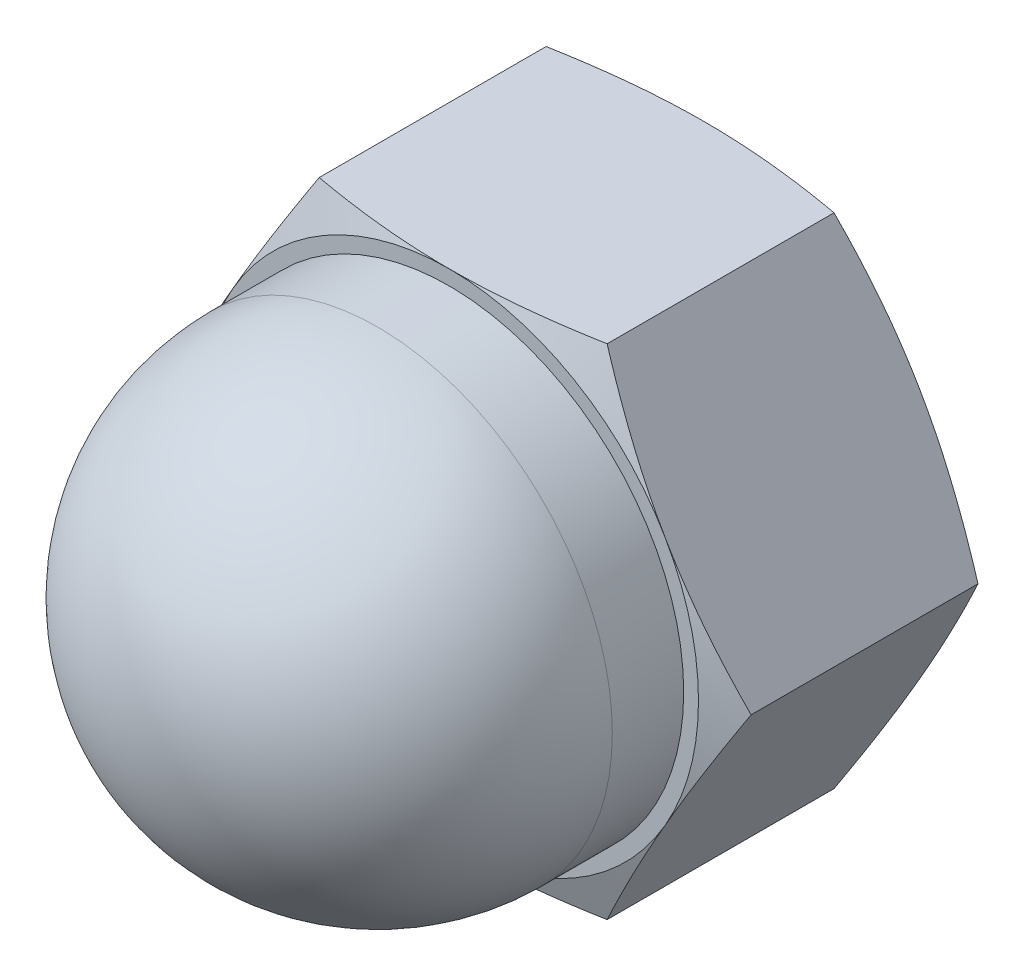
SolidWorks part; units mm, degrees
ref_plane "Front" through (0, 0, 0) normal (0, 0, 1) x (1, 0, 0)
ref_plane "Top" through (0, 0, 0) normal (0, 1, 0) x (1, 0, 0)
ref_plane "Right" through (0, 0, 0) normal (1, 0, 0) x (0, 0, -1)
sketch "Sketch1" plane through (0, 0, 0) normal (0, 0, 1) x (1, 0, 0)
  line L1 (5.6465, 0) -> (2.8232, 4.89)
  line L2 (2.8232, 4.89) -> (-2.8232, 4.89)
  line L3 (-2.8232, 4.89) -> (-5.6465, 0)
  line L4 (-5.6465, 0) -> (-2.8232, -4.89)
  line L5 (-2.8232, -4.89) -> (2.8232, -4.89)
  line L6 (2.8232, -4.89) -> (5.6465, 0)
  circle A0 centre (0, 0) radius 4.89 construction
  circle A1 centre (0, 0) radius 2.5
extrude "BaseNut" add sketch "Sketch1" against normal blind 5
cosmetic thread "ThreadCosmetic1" [suppressed] parameters "D1"=5, "D2"=6
sketch "Sketch2" plane through (0, 0, 0) normal (0, 1, 0) x (1, 0, 0)
  line L0 (-4.89, 5) -> (-5.6465, 5)
  line L2 (-5.6465, 5) -> (-5.6465, 4.7247)
  line L4 (-5.6465, 4.7247) -> (-4.89, 5)
  line L5 (0, 3.3779) -> (0, -9.1399) construction
  line L7 (-7.1748, 2.5) -> (8.0192, 2.5) construction
  line L8 (-5.6465, 0.2753) -> (-4.89, 0)
  line L9 (-5.6465, 0) -> (-5.6465, 0.2753)
  line L10 (-4.89, 0) -> (-5.6465, 0)
  line L11 (-2.8232, 0) -> (-5.6465, 0) construction
  dimension "D1" = 9.78
  dimension "h1" = 2.5
revolve "DoubleChamfer" cut sketch "Sketch2" angle 360 about L5
sketch "Sketch3" plane through (-4.6, 0, -6) normal (0, 1, 0) x (-1, 0, 0)
  line L1 (-9.2, 7.4) -> (-9.2, 6)
  line L3 (-4.6, 12) -> (-4.6, 0) construction
  line L4 (0.29, 6) -> (-9.49, 6) construction
  line L5 (-7.85, 6) -> (-9.2, 6)
  line L6 (-7.85, 8) -> (-7.85, 6)
  line L7 (-7.85, 8) -> (-4.6, 11)
  line L8 (-4.6, 12) -> (-4.6, 11)
  line L10 (-4.6, 1) -> (-0.3651, 1) construction
  arc A0 (-4.6, 12) -> (-9.2, 7.4) centre (-4.6, 7.4) ccw
  dimension "l" = 7
  dimension "h2" = 10
  dimension "m" = 11
revolve "Crown" add sketch "Sketch3" angle 360 about L3
chamfer "EndChamfer" distance 0.65 angle 30 1 edges at (2.5, 0, -5) first distance on face at (2.5, 0, -5)
sketch "Sketch4" plane through (0, 0, 0) normal (0, 1, 0) x (1, 0, 0)
  line L0 (0, 7.0607) -> (0, 2.3352) construction
  line L1 (2, 4.6) -> (2.5, 4.6)
  line L2 (2.5, 4.6) -> (2.933, 4.35)
  line L3 (2.933, 4.35) -> (2.5, 4.1)
  line L4 (2.5, 4.1) -> (2, 4.1)
  line L5 (2, 4.1) -> (2, 4.6)
  line L6 (-2.5, 4.35) -> (2.5, 4.35) construction
  dimension "D1" = 0.5
  dimension "D2" = 5
revolve "Cut-Revolve10" [suppressed] cut sketch "Sketch4" angle 360 about L0
pattern_linear "LPattern10" [suppressed] count 8 spacing 0.6 along (0, 0, 1) of bodies 104
equation "\"h1@Sketch2\" = \"h@BaseNut\" / 2"
equation "\"h2@Sketch3\" = \"m@Sketch3\"-1"
equation "\"D1@Sketch2\" =  \"s@Sketch1\""
equation "\"D2@Sketch4\" = \"d@Sketch1\""
equation "\"D1@Sketch4\" =  ( \"D2@ThreadCosmetic1\" - \"d@Sketch1\" )  / 2"
equation "\"D3@LPattern10\" = \"D1@Sketch4\" * 1.2"
equation "\"D1@LPattern10\" = \"h@BaseNut\" / \"D3@LPattern10\""
